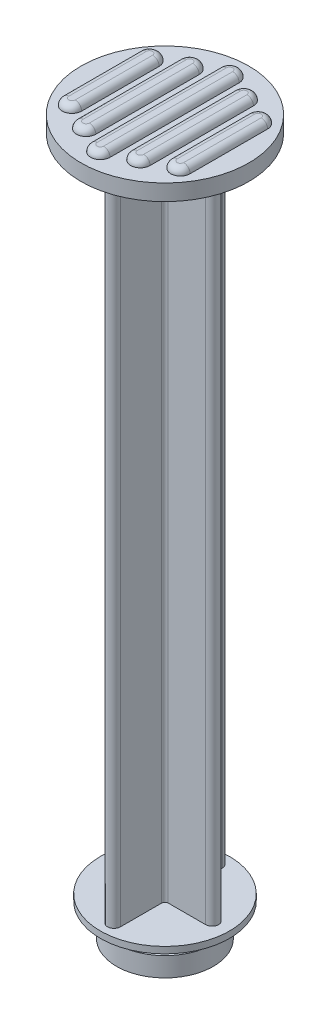
SolidWorks part; units mm, degrees
ref_plane "Front Plane" through (0, 0, 0) normal (0, 0, 1) x (1, 0, 0)
ref_plane "Top Plane" through (0, 0, 0) normal (0, 1, 0) x (1, 0, 0)
ref_plane "Right Plane" through (0, 0, 0) normal (1, 0, 0) x (0, 0, -1)
sketch "Sketch1" plane through (0, 0, 0) normal (0, 0, 1) x (1, 0, 0)
  line L0 (0, 0) -> (7.5, 0)
  line L1 (7.5, 0) -> (7.5, 3)
  line L2 (7.5, 3) -> (6, 3)
  line L3 (6, 3) -> (6, 5)
  line L4 (6, 5) -> (10, 5)
  line L5 (10, 5) -> (10, 6)
  line L6 (10, 6) -> (0, 6)
  line L7 (0, 6) -> (0, 0)
  point P5 (6, 4)
  dimension "D1" = 7.5
  dimension "D2" = 3
  dimension "D3" = 1
  dimension "D4" = 2
  dimension "D5" = 10
  dimension "D6" = 6
revolve "Revolve1" add sketch "Sketch1" angle 360 about L7
sketch "Sketch2" plane through (0, 6, 0) normal (0, 1, 0) x (1, 0, 0)
  line L0 (0, 10) -> (0, -10) construction
  line L1 (-10, 0) -> (10, 0) construction
  line L2 (-1, 7.8919) -> (-1, 1.5)
  line L3 (-7.3049, -1) -> (-1.5, -1)
  line L4 (1, 7.8919) -> (1, 1.5)
  line L5 (-7.3049, 1) -> (-1.5, 1)
  line L6 (-1, -1.5) -> (-1, -7.8919)
  line L7 (-10, -1) -> (10, -1) construction
  line L8 (-10, 1) -> (10, 1) construction
  line L9 (-1, 10) -> (-1, -10) construction
  line L10 (1, 10) -> (1, -10) construction
  line L11 (1, -1.5) -> (1, -7.8919)
  line L12 (1.5, -1) -> (7.3049, -1)
  line L13 (1.5, 1) -> (7.3049, 1)
  circle A0 centre (0, 0) radius 10 construction
  arc A1 (1, 7.8919) -> (-1, 7.8919) centre (0, 7.8919) ccw
  arc A2 (-7.3049, 1) -> (-7.3049, -1) centre (-7.3049, 0) ccw
  arc A3 (1, -7.8919) -> (-1, -7.8919) centre (0, -7.8919) cw
  arc A4 (7.3049, 1) -> (7.3049, -1) centre (7.3049, 0) cw
  arc A5 (-1, -1.5) -> (-1.5, -1) centre (-1.5, -1.5) ccw
  arc A6 (1, -1.5) -> (1.5, -1) centre (1.5, -1.5) cw
  arc A7 (1, 1.5) -> (1.5, 1) centre (1.5, 1.5) ccw
  arc A8 (-1, 1.5) -> (-1.5, 1) centre (-1.5, 1.5) cw
  point P35 (1, -1)
  point P38 (1, 1)
  dimension "D3" = 0.5
  dimension "D1" = 1
  dimension "D2" = 1
extrude "Boss-Extrude1" add sketch "Sketch2" along normal blind 102
sketch "Sketch3" plane through (0, 108, 0) normal (0, 1, 0) x (1, 0, 0)
  circle A0 centre (0, 0) radius 13
  dimension "D1" = 26
extrude "Boss-Extrude3" add sketch "Sketch3" along normal blind 2.5
sketch "Sketch4" plane through (0, 110.5, 0) normal (0, 1, 0) x (1, 0, 0)
  line L0 (0, 13) -> (0, -13) construction
  line L1 (-4.2, 8) -> (-4.2, -8) construction
  line L2 (-8.4, 6) -> (-8.4, -6) construction
  line L3 (-13, 0) -> (13, 0) construction
  line L4 (0, 10) -> (0, 0) construction
  line L5 (0, 0) -> (0, -10) construction
  line L6 (-1.5, 10) -> (-1.5, -10)
  line L7 (-5.7, 8) -> (-5.7, -8)
  line L8 (-9.9, 6) -> (-9.9, -6)
  line L9 (1.5, 10) -> (1.5, -10)
  line L10 (-2.7, 8) -> (-2.7, -8)
  line L11 (-6.9, 6) -> (-6.9, -6)
  line L12 (6.9, 6) -> (6.9, -6)
  line L13 (1.5, 13) -> (1.5, -13) construction
  line L14 (-1.5, 13) -> (-1.5, -13) construction
  line L15 (9.9, 6) -> (9.9, -6)
  line L16 (2.7, 8) -> (2.7, -8)
  line L17 (5.7, 8) -> (5.7, -8)
  circle A0 centre (0, 0) radius 13 construction
  arc A1 (1.5, 10) -> (-1.5, 10) centre (0, 10) ccw
  arc A3 (-6.9, 6) -> (-9.9, 6) centre (-8.4, 6) ccw
  arc A4 (-9.9, -6) -> (-6.9, -6) centre (-8.4, -6) ccw
  arc A5 (-5.7, -8) -> (-2.7, -8) centre (-4.2, -8) ccw
  arc A6 (-1.5, -10) -> (1.5, -10) centre (0, -10) ccw
  arc A7 (-2.7, 8) -> (-5.7, 8) centre (-4.2, 8) ccw
  arc A8 (9.9, -6) -> (6.9, -6) centre (8.4, -6) cw
  arc A9 (6.9, 6) -> (9.9, 6) centre (8.4, 6) cw
  arc A10 (5.7, -8) -> (2.7, -8) centre (4.2, -8) cw
  arc A11 (2.7, 8) -> (5.7, 8) centre (4.2, 8) cw
  point P17 (-5.7, 8)
  dimension "D1" = 4.2
  dimension "D2" = 4.2
  dimension "D3" = 6
  dimension "D4" = 8
  dimension "D5" = 10
  dimension "D6" = 12
  dimension "D7" = 16
  dimension "D8" = 20
  dimension "D9" = 1.5
  dimension "D10" = 1.5
extrude "Boss-Extrude4" add sketch "Sketch4" along normal blind 1
fillet "Fillet1" radius 1 20 edges at (9.9, 111.5, 0) (8.4, 111.5, 7.5) (6.9, 111.5, 0) (8.4, 111.5, -7.5) (2.7, 111.5, 0) (4.2, 111.5, -9.5) (5.7, 111.5, 0) (4.2, 111.5, 9.5) (1.5, 111.5, 0) (0, 111.5, 11.5) (-1.5, 111.5, 0) (0, 111.5, -11.5) (-5.7, 111.5, 0) (-4.2, 111.5, -9.5) (-2.7, 111.5, 0) (-4.2, 111.5, 9.5) (-6.9, 111.5, 0) (-8.4, 111.5, 7.5) (-9.9, 111.5, 0) (-8.4, 111.5, -7.5)
